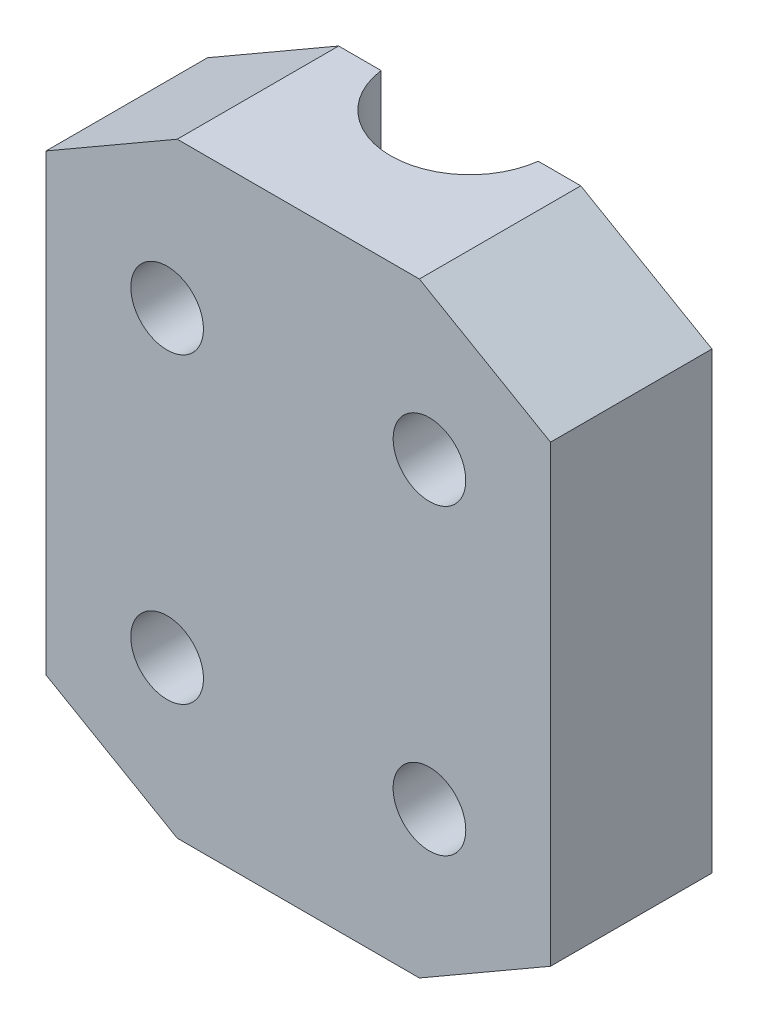
SolidWorks part; units mm, degrees
ref_plane "Piano frontale" through (0, 0, 0) normal (0, 0, 1) x (1, 0, 0)
ref_plane "Piano superiore" through (0, 0, 0) normal (0, 1, 0) x (1, 0, 0)
ref_plane "Piano destro" through (0, 0, 0) normal (1, 0, 0) x (0, 0, -1)
sketch "Schizzo1" plane through (0, 0, 0) normal (0, 0, 1) x (1, 0, 0)
  line L0 (0, -15) -> (0, 15) construction
  line L1 (0, 0) -> (12.5, 0) construction
  line L2 (12.5, -11.2472) -> (12.5, 11.2472)
  line L3 (-6, 15) -> (6, 15)
  line L4 (-12.5, 11.2472) -> (-6, 15)
  line L5 (-12.5, -11.2472) -> (-12.5, 11.2472)
  line L6 (12.5, -11.2472) -> (6, -15)
  line L7 (-12.5, -11.2472) -> (-6, -15)
  line L8 (12.5, 11.2472) -> (6, 15)
  line L9 (-6, -15) -> (6, -15)
  circle A0 centre (-6.5, 7.5) radius 1.8
  circle A1 centre (6.5, -7.5) radius 1.8
  circle A2 centre (-6.5, -7.5) radius 1.8
  circle A3 centre (6.5, 7.5) radius 1.8
  point P21 (-12.5, 0)
  dimension "D4" = 7.5
  dimension "D6" = 3.6
  dimension "D1" = 120
  dimension "D2" = 15
  dimension "D3" = 12.5
  dimension "D5" = 6
  dimension "D7" = 6
extrude "Main Body" add sketch "Schizzo1" along normal blind 8
sketch "Schizzo2" plane through (0, 15, 0) normal (0, 1, 0) x (1, 0, 0)
  line L0 (0, 0.5) -> (0, 0) construction
  line L1 (6, 0) -> (-6, 0) construction
  circle A0 centre (0, 0.5) radius 3.925
  dimension "D1" = 7.85
  dimension "D2" = 0.5
extrude "Threaded rod" cut sketch "Schizzo2" against normal blind 15
sketch "Schizzo4" plane through (0, -15, 0) normal (0, -1, 0) x (1, 0, 0)
  arc A0 (3.893, 0) -> (-3.893, 0) centre (0, -0.5) ccw construction
  arc A1 (3.893, 0) -> (-3.893, 0) centre (0, -0.5) ccw construction
  circle A2 centre (0, -0.5) radius 3.4325
  dimension "D1" = 6.865
extrude "Motor shaft" cut sketch "Schizzo4" against normal up to surface (15 mm away) up to face at (0, 0, 1.7125)
ref_axis "Threaded rod axis" through (0, 0, -0.5) along (0, 1, 0)
ref_axis "Shaft" through (0, 0, -0.5) along (0, -1, 0)
ref_axis "Hole axis 1" through (6.5, -7.5, 5) along (0, 0, -1)
ref_axis "Hole axis 2" through (6.5, 7.5, 5) along (0, 0, -1)
ref_axis "Hole axis 3" through (-6.5, -7.5, 5) along (0, 0, -1)
ref_axis "Hole axis 4" through (-6.5, 7.5, 5) along (0, 0, -1)
